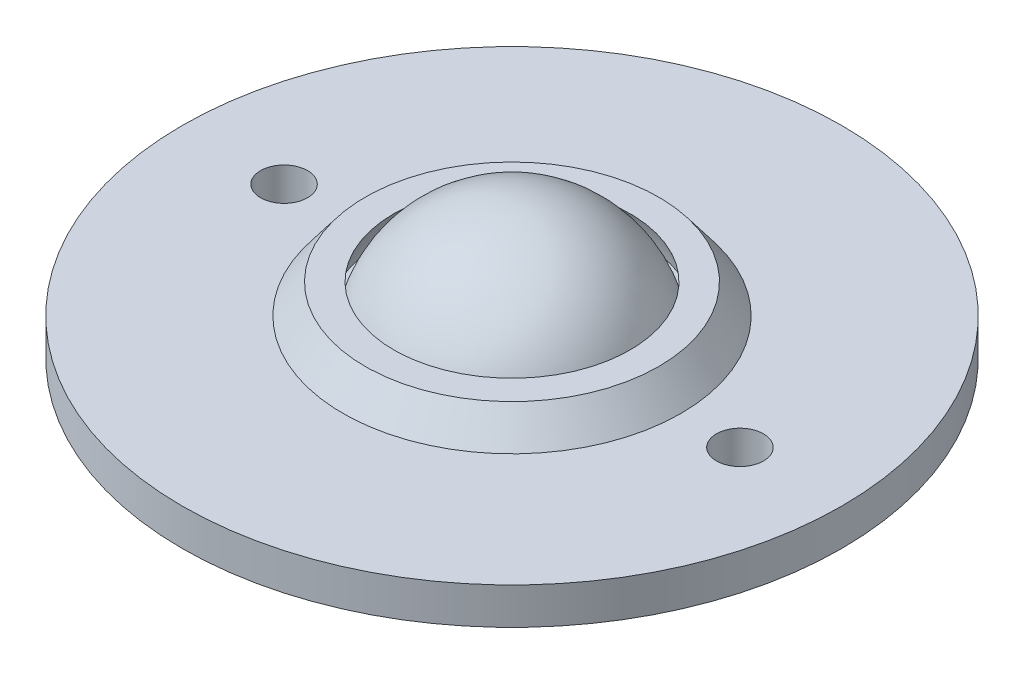
SolidWorks part; units mm, degrees
ref_plane "前视基准面" through (0, 0, 0) normal (0, 0, 1) x (1, 0, 0)
ref_plane "上视基准面" through (0, 0, 0) normal (0, 1, 0) x (1, 0, 0)
ref_plane "右视基准面" through (0, 0, 0) normal (1, 0, 0) x (0, 0, -1)
sketch "草图1" plane through (0, 0, 0) normal (0, 0, 1) x (1, 0, 0)
  line L0 (-8.761, 0.9615) -> (8.761, 0.9615) construction
  line L1 (0, 0) -> (0, 2.5853) construction
  line L2 (-22.4202, 0.9615) -> (-11.5, 0.9615)
  line L3 (-22.4202, 0.9615) -> (-22.4202, -1.5385)
  line L4 (-22.4202, -1.5385) -> (-12.405, -1.5385)
  line L5 (22.5798, 0.9615) -> (22.5798, -1.5385)
  line L6 (-11.5, 0.9615) -> (-9.9788, 2.9615)
  line L7 (-9.9788, 2.9615) -> (-8.032, 2.9615)
  line L8 (11.5, 0.9615) -> (9.9788, 2.9615)
  line L9 (8.032, 2.9615) -> (9.9788, 2.9615)
  line L10 (0, 0.9615) -> (8.761, 0.9615)
  line L11 (0, 0.9615) -> (-8.761, 0.9615)
  line L12 (0, 0.9615) -> (0, -12.5)
  line L13 (0, 7.5) -> (0, 0.9615)
  line L22 (11.5, 0.9615) -> (22.5798, 0.9615)
  line L23 (12.405, -1.5385) -> (22.5798, -1.5385)
  arc A0 (-8.3485, 0.9615) -> (8.3485, 0.9615) centre (0, -1.099) cw
  arc A1 (-12.405, -1.5385) -> (12.405, -1.5385) centre (0, 0) ccw
  arc A2 (8.761, 0.9615) -> (8.032, 2.9615) centre (0, -1.099) ccw
  arc A3 (-8.032, 2.9615) -> (-8.761, 0.9615) centre (0, -1.099) ccw
  point P0 (0, 0.9615)
  point P10 (0, 0.9615)
  point P14 (0, 2.9615)
  point P21 (0, 7.5)
  dimension "D1" = 12.5
  dimension "D6" = 7.5
  dimension "D7" = 9
  dimension "D2" = 2.5
  dimension "D3" = 45
  dimension "D4" = 23
  dimension "D5" = 2
other "对齐组1"
revolve "旋转5" add sketch "草图1" angle 360 about L1 region at (-7.3334, -3.9208, 0)
revolve "旋转8" add sketch "草图1<6>" angle 360 about L1 region at (3.3859, 3.6868, 0)
sketch "草图1<6>" plane through (0, 0, 0) normal (0, 0, 1) x (1, 0, 0) same geometry as "草图1"
sketch "草图2" plane through (0, 0.9615, 0) normal (0, 1, 0) x (1, 0, 0)
  line L0 (-22.4202, 0) -> (22.4202, 0) construction
  line L1 (0, 22.4202) -> (0, -22.4202) construction
  circle A0 centre (0, 0) radius 22.4202 construction
  circle A1 centre (-15.5, 0) radius 1.6
  circle A2 centre (15.5, 0) radius 1.6
  dimension "D1" = 15.5
  dimension "D2" = 3.2
extrude "切除-拉伸1" cut sketch "草图2" against normal blind 10
sketch "草图4" plane through (0, 0, 0) normal (1, 0, 0) x (0, 0, -1)
  line L0 (0, 7.5) -> (0, -12.5)
  arc A0 (8.3485, 0.9615) -> (-8.3485, 0.9615) centre (0, -1.099) ccw construction
  arc A1 (-12.405, -1.5385) -> (12.405, -1.5385) centre (0, 0) ccw construction
  dimension "D1" = 20
